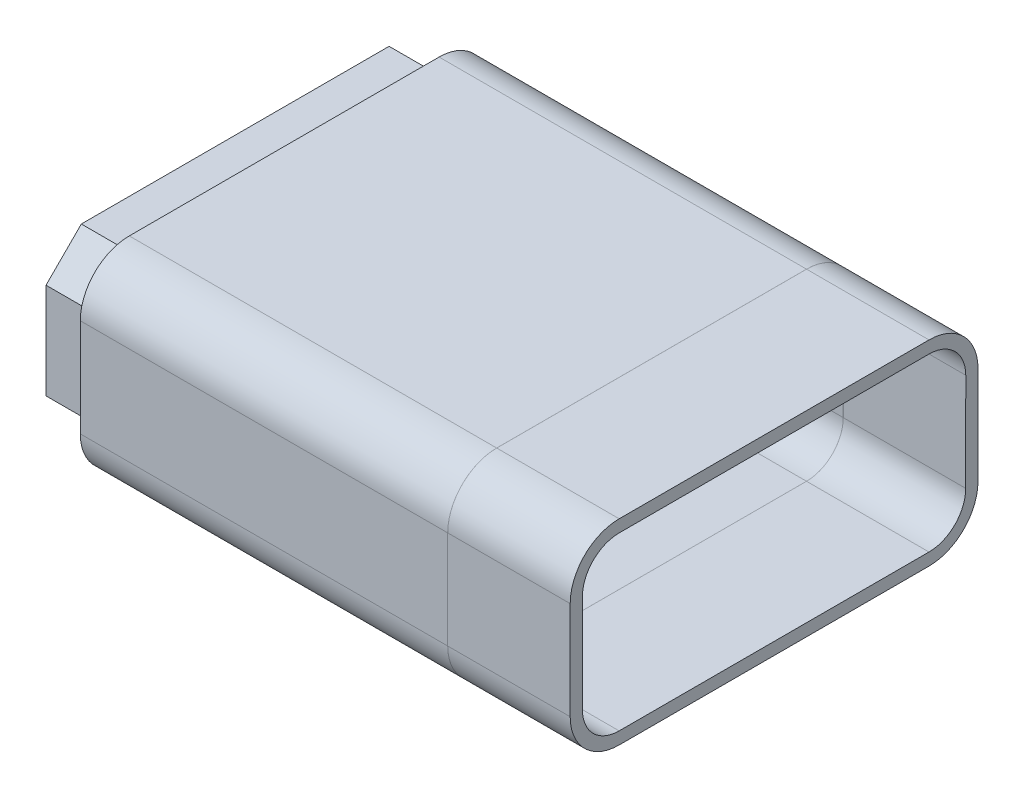
SolidWorks part; units mm, degrees
ref_plane "Front" through (0, 0, 0) normal (0, 0, 1) x (1, 0, 0)
ref_plane "Top" through (0, 0, 0) normal (0, 1, 0) x (1, 0, 0)
ref_plane "Right" through (0, 0, 0) normal (1, 0, 0) x (0, 0, -1)
sketch "Sketch2path" plane through (0, 0, 0) normal (0, 0, 1) x (1, 0, 0)
  line L0 (30.0026, 0) -> (40.0026, -0.0017)
  line L1 (0, 0) -> (30, 0)
  arc A1 (30, 0) -> (30.0026, 0) centre (30, -15) cw
  point P5 (30.0013, 0)
  dimension "D1" = 30
  dimension "D2" = 0.01
  dimension "D4" = 15
  dimension "D3" = 10
sketch "Sketch3" plane through (0, 0, 0) normal (1, 0, 0) x (0, 0, -1)
  line L0 (-16.65, -4) -> (-16.65, 4)
  line L1 (-12.65, 8) -> (12.65, 8)
  line L2 (16.65, 4) -> (16.65, -4)
  line L3 (12.65, -8) -> (-12.65, -8)
  line L4 (-15.65, -4) -> (-15.65, 4)
  line L5 (12.65, -7) -> (-12.65, -7)
  line L6 (0, 91.8161) -> (0, -91.8161) construction
  line L12 (15.65, 4) -> (15.65, -4)
  line L13 (-12.65, 7) -> (12.65, 7)
  arc A0 (-12.65, 8) -> (-16.65, 4) centre (-12.65, 4) ccw
  arc A1 (16.65, 4) -> (12.65, 8) centre (12.65, 4) ccw
  arc A2 (12.65, -8) -> (16.65, -4) centre (12.65, -4) ccw
  arc A3 (-16.65, -4) -> (-12.65, -8) centre (-12.65, -4) ccw
  arc A4 (-12.65, 7) -> (-15.65, 4) centre (-12.65, 4) ccw
  arc A5 (-15.65, -4) -> (-12.65, -7) centre (-12.65, -4) ccw
  arc A10 (12.65, -7) -> (15.65, -4) centre (12.65, -4) ccw
  arc A11 (15.65, 4) -> (12.65, 7) centre (12.65, 4) ccw
  dimension "D1" = 4
  dimension "D2" = 3
  dimension "D3" = 15.65
  dimension "D4" = 15.65
  dimension "D5" = 7
  dimension "D6" = 7
sweep "Sweep1" add profiles "Sketch3" path "Sketch2path"
ref_point "Point1S1"
ref_point "Point2S3"
ref_axis "os podluzna S1" through (0, 0, 0) along (-1, 0, 0)
ref_axis "os podluzna S3" through (40.0026, -0.0017, 0) along (1, -0.0002, 0)
sketch "Sketch14" plane through (0, 0, 0) normal (-1, 0, 0) x (0, 0, 1)
  line L0 (-15.65, -4) -> (-15.65, 4) construction
  line L1 (12.65, -7) -> (-12.65, -7) construction
  line L2 (15.65, 4) -> (15.65, -4) construction
  line L3 (-12.65, 7) -> (12.65, 7) construction
  line L12 (-15.65, -4) -> (-15.65, 4)
  line L13 (12.65, -7) -> (-12.65, -7)
  line L14 (15.65, 4) -> (15.65, -4)
  line L15 (-12.65, 7) -> (12.65, 7)
  line L16 (-12.65, 5.8) -> (12.65, 5.8)
  line L17 (14.45, 4) -> (14.45, -4)
  line L18 (12.65, -5.8) -> (-12.65, -5.8)
  line L19 (-14.45, -4) -> (-14.45, 4)
  arc A0 (-15.65, -4) -> (-12.65, -7) centre (-12.65, -4) ccw construction
  arc A1 (12.65, -7) -> (15.65, -4) centre (12.65, -4) ccw construction
  arc A2 (15.65, 4) -> (12.65, 7) centre (12.65, 4) ccw construction
  arc A3 (-12.65, 7) -> (-15.65, 4) centre (-12.65, 4) ccw construction
  arc A12 (-15.65, -4) -> (-12.65, -7) centre (-12.65, -4) ccw
  arc A13 (12.65, -7) -> (15.65, -4) centre (12.65, -4) ccw
  arc A14 (15.65, 4) -> (12.65, 7) centre (12.65, 4) ccw
  arc A15 (-12.65, 7) -> (-15.65, 4) centre (-12.65, 4) ccw
  arc A16 (14.45, 4) -> (12.65, 5.8) centre (12.65, 4) ccw
  arc A17 (12.65, -5.8) -> (14.45, -4) centre (12.65, -4) ccw
  arc A18 (-14.45, -4) -> (-12.65, -5.8) centre (-12.65, -4) ccw
  arc A19 (-12.65, 5.8) -> (-14.45, 4) centre (-12.65, 4) ccw
  dimension "D2" = 1.2
extrude "Boss-Extrude7" add sketch "Sketch14" along normal mid plane 8
sketch "Sketch15" plane through (-4, 0, 0) normal (-1, 0, 0) x (0, 0, 1)
  line L0 (-15.45, 4) -> (-15.45, -4)
  line L1 (-12.65, -6.8) -> (12.65, -6.8)
  line L2 (15.45, -4) -> (15.45, 4)
  line L3 (12.65, 6.8) -> (-12.65, 6.8)
  line L4 (-12.65, -7) -> (12.65, -7)
  line L5 (15.65, -4) -> (15.65, 4)
  line L6 (12.65, 7) -> (-12.65, 7)
  line L7 (-15.65, 4) -> (-15.65, -4)
  line L8 (-12.65, -7) -> (12.65, -7)
  line L9 (15.65, -4) -> (15.65, 4)
  line L10 (12.65, 7) -> (-12.65, 7)
  line L11 (-15.65, 4) -> (-15.65, -4)
  arc A0 (-12.65, 6.8) -> (-15.45, 4) centre (-12.65, 4) ccw
  arc A1 (-15.45, -4) -> (-12.65, -6.8) centre (-12.65, -4) ccw
  arc A2 (12.65, -6.8) -> (15.45, -4) centre (12.65, -4) ccw
  arc A3 (15.45, 4) -> (12.65, 6.8) centre (12.65, 4) ccw
  arc A4 (-15.65, -4) -> (-12.65, -7) centre (-12.65, -4) ccw
  arc A5 (12.65, -7) -> (15.65, -4) centre (12.65, -4) ccw
  arc A6 (15.65, 4) -> (12.65, 7) centre (12.65, 4) ccw
  arc A7 (-12.65, 7) -> (-15.65, 4) centre (-12.65, 4) ccw
  arc A8 (-15.65, -4) -> (-12.65, -7) centre (-12.65, -4) ccw
  arc A9 (12.65, -7) -> (15.65, -4) centre (12.65, -4) ccw
  arc A10 (15.65, 4) -> (12.65, 7) centre (12.65, 4) ccw
  arc A11 (-12.65, 7) -> (-15.65, 4) centre (-12.65, 4) ccw
  dimension "D1" = 0
  dimension "D2" = 0.2
extrude "Cut-Extrude1" cut sketch "Sketch15" against normal up to surface (4 mm away) up to face at (0, 0, 0)
sketch "Sketch20" plane through (-4, 0, 0) normal (-1, 0, 0) x (0, 0, 1)
  line L0 (16.65, 2.7151) -> (16.65, 4)
  line L1 (-11.3651, 8) -> (-12.65, 8)
  line L2 (11.3651, -8) -> (12.65, -8)
  line L3 (-16.65, -2.7151) -> (-16.65, -4)
  line L8 (-16.65, -2.7151) -> (-11.3651, -8)
  line L9 (-16.65, 2.7151) -> (-11.3651, 8)
  line L10 (11.3651, 8) -> (16.65, 2.7151)
  line L11 (16.65, -2.7151) -> (11.3651, -8)
  line L16 (16.65, -4) -> (16.65, 4)
  line L17 (12.65, 8) -> (-12.65, 8)
  line L18 (-16.65, 4) -> (-16.65, -4)
  line L19 (-12.65, -8) -> (12.65, -8)
  line L20 (16.65, -4) -> (16.65, -2.7151)
  line L21 (12.65, 8) -> (11.3651, 8)
  line L22 (-16.65, 4) -> (-16.65, 2.7151)
  line L23 (-12.65, -8) -> (-11.3651, -8)
  arc A16 (12.65, -8) -> (16.65, -4) centre (12.65, -4) ccw
  arc A17 (16.65, 4) -> (12.65, 8) centre (12.65, 4) ccw
  arc A18 (-12.65, 8) -> (-16.65, 4) centre (-12.65, 4) ccw
  arc A19 (-16.65, -4) -> (-12.65, -8) centre (-12.65, -4) ccw
  arc A20 (12.65, -8) -> (16.65, -4) centre (12.65, -4) ccw
  arc A21 (16.65, 4) -> (12.65, 8) centre (12.65, 4) ccw
  arc A22 (-12.65, 8) -> (-16.65, 4) centre (-12.65, 4) ccw
  arc A23 (-16.65, -4) -> (-12.65, -8) centre (-12.65, -4) ccw
  dimension "D3" = 0
extrude "Cut-Extrude5 sciecia" cut sketch "Sketch20" against normal up to vertex (4 mm away) up to point (0, 4, 16.65)
